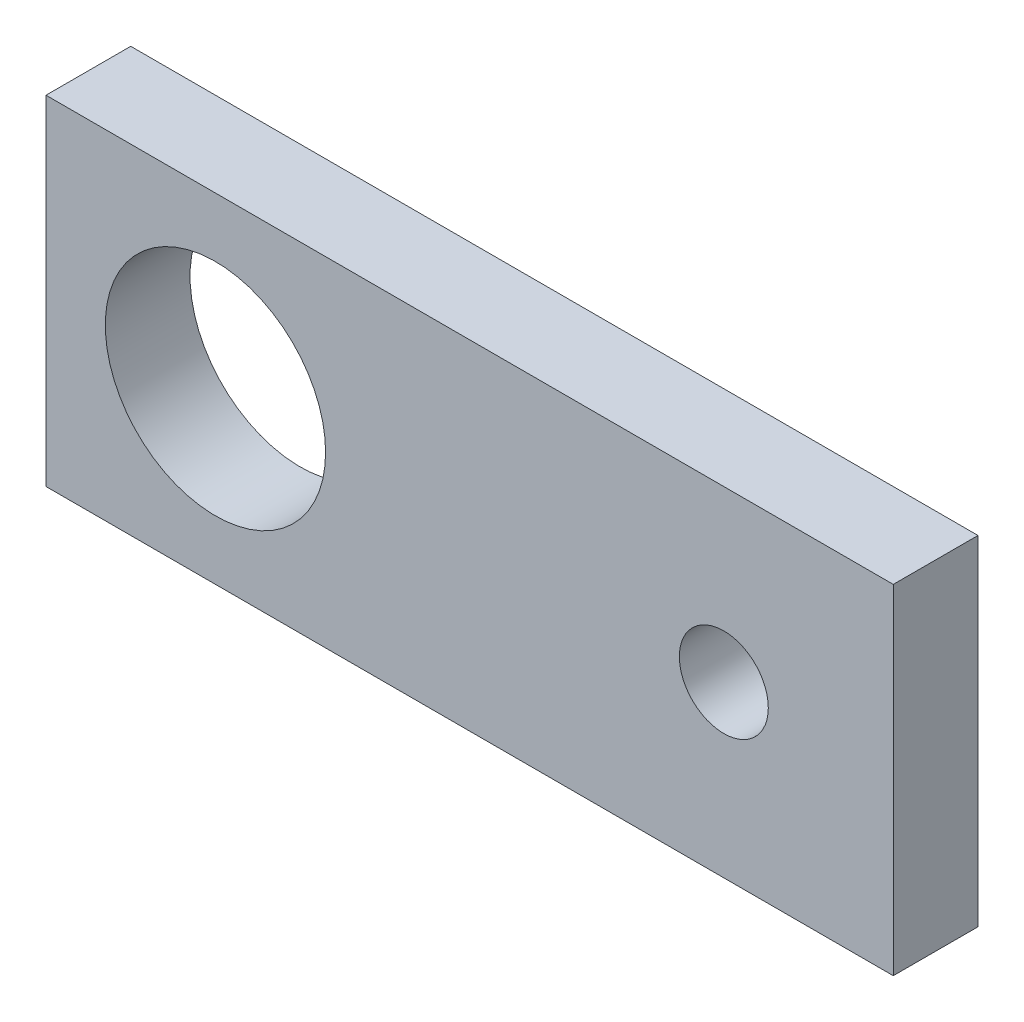
SolidWorks part; units mm, degrees
ref_plane "Front Plane" through (0, 0, 0) normal (0, 0, 1) x (1, 0, 0)
ref_plane "Top Plane" through (0, 0, 0) normal (0, 1, 0) x (1, 0, 0)
ref_plane "Right Plane" through (0, 0, 0) normal (1, 0, 0) x (0, 0, -1)
sketch "Sketch1" plane through (0, 0, 0) normal (0, 0, 1) x (1, 0, 0)
  line L1 (-4, -4) -> (16, -4)
  line L2 (-4, -4) -> (-4, 4)
  line L3 (-4, 4) -> (16, 4)
  line L4 (16, -4) -> (16, 4)
  circle A0 centre (0, 0) radius 2.6
  circle A1 centre (12, 0) radius 1.05
extrude "R12_Horn_Envelope" add sketch "Sketch1" along normal blind 2
